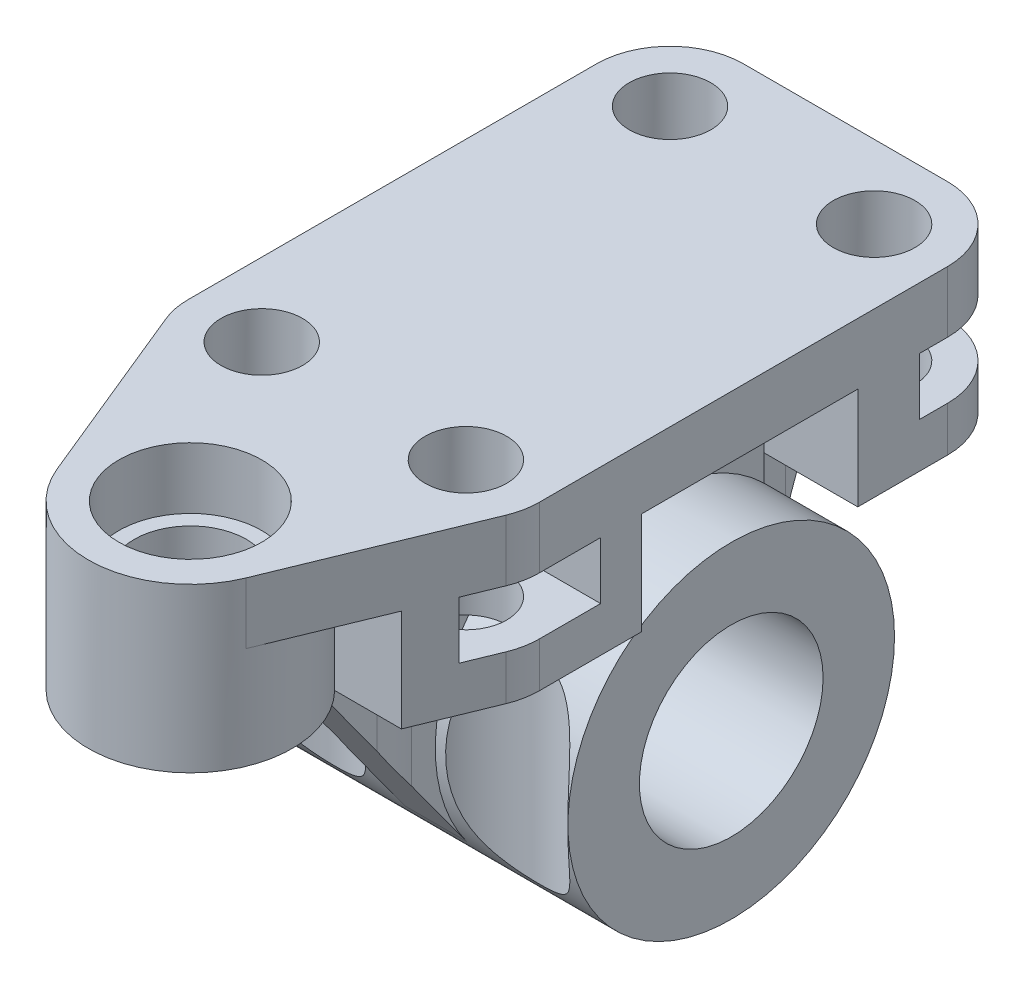
SolidWorks part; units mm, degrees
ref_plane "Front Plane" through (0, 0, 0) normal (0, 0, 1) x (1, 0, 0)
ref_plane "Top Plane" through (0, 0, 0) normal (0, 1, 0) x (1, 0, 0)
ref_plane "Right Plane" through (0, 0, 0) normal (1, 0, 0) x (0, 0, -1)
sketch "Sketch1" plane through (0, 0, 0) normal (1, 0, 0) x (0, 0, -1)
  line L1 (55, 0) -> (-55, 0) construction
  circle A0 centre (0, -15) radius 8
  circle A1 centre (0, -15) radius 4.5
  dimension "D2" = 9
  dimension "D3" = 16
  dimension "D1" = 15
extrude "Boss-Extrude1" add sketch "Sketch1" along normal mid plane 16
ref_axis "Axis1" through (8, -15, 0) along (-1, 0, 0)
ref_plane "Flange Plane" through (0, -2, 0) normal (0, 1, 0) x (-1, 0, 0)
sketch "Sketch2" plane through (0, -2, 0) normal (0, 1, 0) x (1, 0, 0)
  line L0 (8, 0) -> (-8, 0) construction
  line L1 (0, -18.5) -> (0, 16.1506) construction
  line L2 (8, 0) -> (-8, 0) construction
  line L3 (8, -8) -> (8, 8) construction
  line L4 (-8, 8) -> (-8, -8) construction
  line L5 (-5, 13.6) -> (5, 13.6)
  line L6 (-8.3307, -11.3663) -> (-4.6259, -20.3976)
  line L7 (4.6259, -20.3976) -> (8.3307, -11.3663)
  line L8 (-8.6, 10) -> (-8.6, -10)
  line L9 (8.6, -10) -> (8.6, 10)
  circle A0 centre (0, -18.5) radius 3.5
  arc A1 (-4.6259, -20.3976) -> (4.6259, -20.3976) centre (0, -18.5) ccw
  circle A2 centre (5, -10) radius 2
  circle A3 centre (-5, -10) radius 2
  circle A4 centre (5, 10) radius 2
  circle A5 centre (-5, 10) radius 2
  arc A6 (-5, 13.6) -> (-8.6, 10) centre (-5, 10) ccw
  arc A7 (8.6, 10) -> (5, 13.6) centre (5, 10) ccw
  arc A8 (8.3307, -11.3663) -> (8.6, -10) centre (5, -10) ccw
  arc A9 (-8.6, -10) -> (-8.3307, -11.3663) centre (-5, -10) ccw
  dimension "D1" = 7
  dimension "D4" = 4
  dimension "D6" = 10
  dimension "D7" = 7.2
  dimension "D2" = 18.5
  dimension "D3" = 10
  dimension "D5" = 20
extrude "Boss-Extrude Flange" add sketch "Sketch2" along normal blind 2 and the other way blind 1 separate body
ref_axis "LED Axis" through (0, -3, 18.5) along (0, 1, 0)
sketch "Sketch3" plane through (0, -3, 0) normal (0, -1, 0) x (1, 0, 0)
  line L0 (8.6, 10) -> (8.6, -10) construction
  line L1 (5, -13.6) -> (0.6, -13.6)
  line L2 (8.6, -10) -> (8.6, -5.6)
  line L3 (8.6, -5.6) -> (0.6, -5.6)
  line L4 (0.6, -13.6) -> (0.6, -5.6)
  line L5 (10.3778, -13.6) -> (0.6, -5.6) construction
  line L6 (8.6, -5.6) -> (0.6, -13.6) construction
  line L7 (-0.6, -13.6) -> (-5, -13.6)
  line L8 (-0.6, -13.6) -> (-0.6, -5.6)
  line L9 (-0.6, -5.6) -> (-8.6, -5.6)
  line L10 (-8.6, -10) -> (-8.6, -5.6)
  line L11 (-0.6, -13.6) -> (-8.6, -5.6) construction
  line L12 (-0.6, -5.6) -> (-7.8, -12.8) construction
  line L13 (-1.4, 5) -> (-8.6, 5)
  line L14 (-1.4, 5) -> (-1.4, 8.5)
  line L15 (-3.5707, 15) -> (-6.8401, 15)
  line L16 (-8.6, 5) -> (-8.6, 10)
  line L17 (-1.4, 5) -> (-8.6, 15) construction
  line L18 (-1.4, 15) -> (-8.6, 5) construction
  line L19 (8.6, 5) -> (1.4, 5)
  line L20 (8.6, 5) -> (8.6, 10)
  line L21 (6.8401, 15) -> (3.5707, 15)
  line L22 (1.4, 5) -> (1.4, 8.5)
  line L23 (8.6, 5) -> (1.4, 15) construction
  line L24 (8.6, 15) -> (1.4, 5) construction
  line L25 (5, -13.6) -> (-5, -13.6) construction
  line L26 (-8.6, -10) -> (-8.6, 10) construction
  line L27 (-8.3307, 11.3663) -> (-4.6259, 20.3976) construction
  line L28 (-8.3307, 11.3663) -> (-6.8401, 15)
  line L29 (8.3307, 11.3663) -> (6.8401, 15)
  line L30 (4.6259, 20.3976) -> (8.3307, 11.3663) construction
  line L32 (1.4, 8.5) -> (-1.4, 8.5)
  arc A0 (-5, -13.6) -> (-8.6, -10) centre (-5, -10) cw
  arc A1 (5, -13.6) -> (8.6, -10) centre (5, -10) ccw
  arc A2 (-8.6, 10) -> (-8.3307, 11.3663) centre (-5, 10) cw
  arc A3 (8.6, 10) -> (8.3307, 11.3663) centre (5, 10) ccw
  arc A4 (8.6, 10) -> (8.3307, 11.3663) centre (5, 10) ccw construction
  circle A5 centre (-5, 10) radius 2
  circle A6 centre (5, 10) radius 2
  circle A7 centre (5, -10) radius 2
  circle A8 centre (-5, -10) radius 2
  circle A9 centre (-5, -10) radius 2 construction
  circle A10 centre (5, -10) radius 2 construction
  circle A11 centre (-5, 10) radius 2 construction
  circle A12 centre (5, 10) radius 2 construction
  arc A13 (3.5707, 15) -> (-3.5707, 15) centre (0, 18.5) ccw
  arc A14 (4.6259, 20.3976) -> (-4.6259, 20.3976) centre (0, 18.5) ccw construction
  point P0 (5, -9.2)
  point P6 (-5, -10)
  point P12 (-5, 10)
  point P18 (5, 10)
  point P57 (0, 0)
  dimension "D1" = 10
  dimension "D2" = 10
  dimension "D3" = 3.5
  dimension "D4" = 8
  dimension "D5" = 8
extrude "Boss-Extrude3" add sketch "Sketch3" along normal blind 5
sketch "Sketch8" plane through (0, 0, 0) normal (1, 0, 0) x (0, 0, -1)
  line L1 (-23.5, -8) -> (-15, -8) construction
  line L2 (-21.25, -2) -> (-22, -2)
  line L3 (-22, -8) -> (-22, -5)
  line L4 (-22, -5) -> (-21.25, -5)
  line L5 (-21.25, -5) -> (-21.25, -2)
  line L6 (-20.3976, 0) -> (-23.5, 0) construction
  line L7 (-18.5, 0) -> (-18.5, -8)
  line L8 (-18.5, -3) -> (-18.5, 0) construction
  line L9 (-18.5, -8) -> (-22, -8)
  line L10 (-22, -2) -> (-22, 0)
  line L11 (-22, 0) -> (-18.5, 0)
  dimension "D1" = 2.75
  dimension "D2" = 3.5
  dimension "D3" = 2
  dimension "D4" = 3
sketch "Sketch4" plane through (0, -3, 0) normal (0, -1, 0) x (1, 0, 0)
  line L0 (8, -8.2679) -> (9.6177, -9.2019)
  line L1 (2, -8.2679) -> (2, -11.7321)
  line L2 (2, -11.7321) -> (5, -13.4641)
  line L3 (-3.5707, 15) -> (-6.8401, 15) construction
  line L4 (6.8401, 15) -> (3.5707, 15) construction
  line L5 (8, -8.2679) -> (5, -6.5359)
  line L6 (5, -6.5359) -> (2, -8.2679)
  line L7 (-7.3435, 7) -> (-8.6, 7)
  line L8 (-8.6, 7) -> (-8.6, 13)
  line L9 (-5.9315, -14.0019) -> (-2, -11.7321)
  line L10 (-2, -11.7321) -> (-2, -8.2679)
  line L11 (-2, -8.2679) -> (-5, -6.5359)
  line L12 (-5, -6.5359) -> (-7.1922, -7.8016)
  line L13 (6.7321, 7) -> (8.6, 7)
  line L14 (-7.3435, 7) -> (-3.2679, 7)
  line L15 (-3.2679, 7) -> (-1.5359, 10)
  line L16 (-1.5359, 10) -> (-3.2679, 13)
  line L17 (-3.2679, 13) -> (-6.1747, 13)
  line L18 (8.6, 7) -> (8.6, 13)
  line L19 (1.5359, 10) -> (3.2679, 7)
  line L20 (3.2679, 7) -> (6.7321, 7)
  line L23 (6.7321, 13) -> (3.2679, 13)
  line L24 (3.2679, 13) -> (1.5359, 10)
  line L25 (9.6177, -9.2019) -> (6.6177, -14.3981)
  line L26 (6.6177, -14.3981) -> (5, -13.4641)
  line L27 (-5.9315, -14.0019) -> (-6.6177, -14.3981)
  line L28 (-6.6177, -14.3981) -> (-9.6177, -9.2019)
  line L29 (-9.6177, -9.2019) -> (-7.1922, -7.8016)
  line L30 (-8.6, 13) -> (-6.1747, 13)
  line L31 (-8, -7.7902) -> (-8, -9.5223) [skipped]
  line L32 (-8.4137, -11.4932) -> (-6.9137, -12.3592) [skipped]
  line L33 (6.5, -12.5981) -> (8, -11.7321) [skipped]
  line L34 (8, -10) -> (8, -8.2679) [skipped]
  line L35 (8.6, 13) -> (6.7321, 13)
  line L36 (-8.7698, 10.5296) -> (-7.9038, 9.0296) [skipped]
  line L37 (-6.6848, 13.0819) -> (-7.1442, 12.2862) [skipped]
  line L39 (7.5981, 8.5) -> (8.4641, 10) [skipped]
  line L40 (7.5981, 11.5) -> (6.7321, 13) [skipped]
  circle A0 centre (5, -10) radius 3 construction
  circle A1 centre (-5, -10) radius 3 construction
  circle A2 centre (-5, 10) radius 3 construction
  circle A3 centre (5, 10) radius 3 construction
  arc A4 (5, -13.6) -> (8.6, -10) centre (5, -10) ccw construction
  arc A5 (-8.6, -10) -> (-5, -13.6) centre (-5, -10) ccw construction
  arc A6 (-8.3307, 11.3663) -> (-8.6, 10) centre (-5, 10) ccw construction
  arc A7 (8.6, 10) -> (8.3307, 11.3663) centre (5, 10) ccw construction
  dimension "D1" = 6
extrude "Cut-Extrude1" cut sketch "Sketch4" along normal blind 2.8 contours L18 L9 L10 | L2 L5 | L17 L14 | L23 L24 L19 L20 | L25 L26 L2 L1 L6 L5 L0 | L28 L29 L12 L11 L10 L9 L27 | L8 L30 L17 L16 L15 L14 L7 | L35 L18 L13 L20 L19 L24 L23 region at (5.4164, -3, -10.2404) region at (-5.4808, -3, 10) region at (-5.4164, -3, -10.2404) region at (5.4808, -3, 10)
sketch "Sketch5" plane through (0, 0, 0) normal (1, 0, 0) x (0, 0, -1)
  line L0 (-15, -8) -> (-6.4654, -19.7116)
  line L1 (-6.4654, -19.7116) -> (7.3974, -18.0461)
  line L2 (7.3974, -18.0461) -> (13.5931, -3)
  line L3 (13.5931, -3) -> (13.6, 0)
  line L4 (9.46, 0) -> (-9.46, 0) construction
  line L5 (13.6, -8) -> (13.6, 0) construction
  line L6 (13.6, 0) -> (-15, 0)
  line L8 (-15, -8) -> (-15, -3) construction
  line L9 (-23.5, -8) -> (-15, -8) construction
  line L13 (-15, 0) -> (-15, -8)
  circle A0 centre (0, -15) radius 8 construction
sketch "Sketch6" plane through (0, -3, 0) normal (0, -1, 0) x (1, 0, 0)
  line L0 (-8.6, 5) -> (-1.4, 5) construction
  line L1 (-4, 5) -> (4, 5)
  line L2 (-4, 5) -> (-4, -5.6)
  line L3 (-4, -5.6) -> (4, -5.6)
  line L4 (4, 5) -> (4, -5.6)
  line L6 (0, 11.9827) -> (0, -3.8159) construction
  line L7 (8.6, -5.6) -> (0.6, -5.6) construction
  dimension "D1" = 8
extrude "Boss-Extrude6" add sketch "Sketch5" along normal mid plane 3
extrude "Boss-Extrude7" add sketch "Sketch6" along normal up to surface (5.755 mm away) up to face at (-8, -15, -8)
sketch "Sketch9" plane through (0, -8, 0) normal (0, -1, 0) x (1, 0, 0)
  circle A0 centre (0, 18.5) radius 3.6
  circle A1 centre (-5, 10) radius 3.6
  circle A2 centre (5, 10) radius 3.6
  circle A3 centre (5, -10) radius 3.6
  circle A4 centre (-5, -10) radius 3.6
  dimension "D1" = 7.2
  dimension "D2" = 7.2
extrude "Cut-Extrude2" cut sketch "Sketch9" along normal through all
sketch "Sketch10" plane through (0, 0, 0) normal (1, 0, 0) x (0, 0, -1)
  circle A0 centre (0, -15) radius 4.5
  circle A2 centre (0, -15) radius 4.5 construction
extrude "Cut-Extrude3" cut sketch "Sketch10" against normal through all and the other way through all
revolve "Cut-Revolve2" cut sketch "Sketch8" angle 360 about axis through (0, -3, 18.5) along (0, 1, 0)
